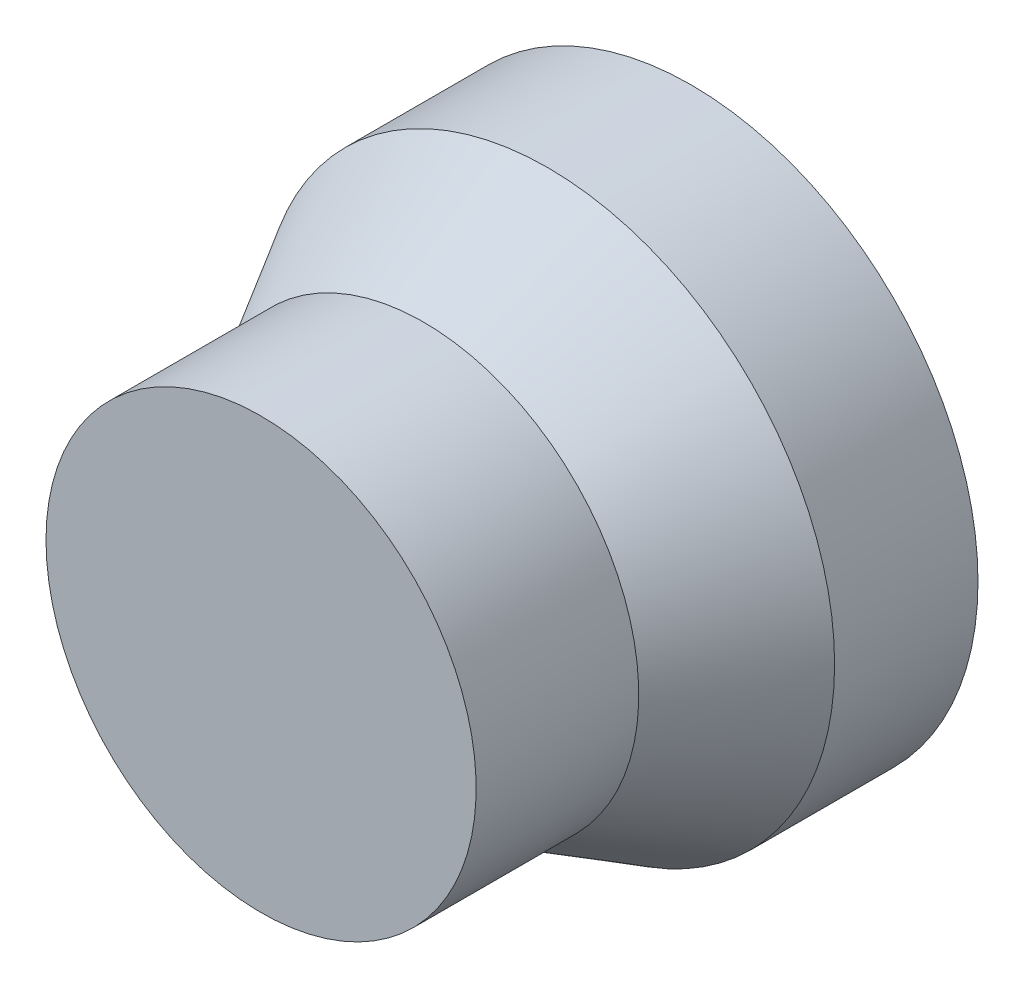
SolidWorks part; units mm, degrees
ref_plane "Front Plane" through (0, 0, 0) normal (0, 0, 1) x (1, 0, 0)
ref_plane "Top Plane" through (0, 0, 0) normal (0, 1, 0) x (1, 0, 0)
ref_plane "Right Plane" through (0, 0, 0) normal (1, 0, 0) x (0, 0, -1)
sketch "Sketch1" plane through (0, 0, 0) normal (0, 1, 0) x (1, 0, 0)
  line L0 (0, 165.5738) -> (0, -211.4754) construction
  line L1 (0, -150) -> (75, -150)
  line L2 (75, -150) -> (75, -93.3013)
  line L3 (75, -93.3013) -> (100, -50)
  line L4 (100, -50) -> (100, 0)
  line L5 (100, 0) -> (0, 0)
  line L6 (0, 0) -> (0, -150)
  dimension "D1" = 75
  dimension "D2" = 100
  dimension "D3" = 150
  dimension "D4" = 50
  dimension "D5" = 30
revolve "Revolve1" add sketch "Sketch1" angle 360 about L0
ref_axis "Axis1" through (0, 0, -7.5) along (0, 0, 1)
equation "\"base_link_diameter\"=75"
equation "\"base_link_length\"=150"
equation "\"D1\"= \"base_link_length\""
equation "\"link2_diameter\"=150"
equation "\"link2_length\"=300"
equation "\"link3_diameter\"=150"
equation "\"link3_length\"=150"
equation "\"link4_diameter\"=150"
equation "\"link4_length\"=150"
equation "\"link5_diameter\"=150"
equation "\"link5_length\"=200"
equation "\"end_effector_diameter\"=150"
equation "\"end_effector_length\"=150"
equation "\"base_link_diameterA\"=200"
equation "\"base_link_diameterB\"=150"
equation "\"D1@Sketch1\"=\"base_link_diameterB\"/2"
equation "\"D2@Sketch1\"=\"base_link_diameterA\"/2"
equation "\"D3@Sketch1\"=\"base_link_length\""
equation "\"base_link_lengthA\"=50"
equation "\"D4@Sketch1\"=\"base_link_lengthA\""
equation "\"link1_diameter\"=150"
equation "\"link1_length\"=150"
